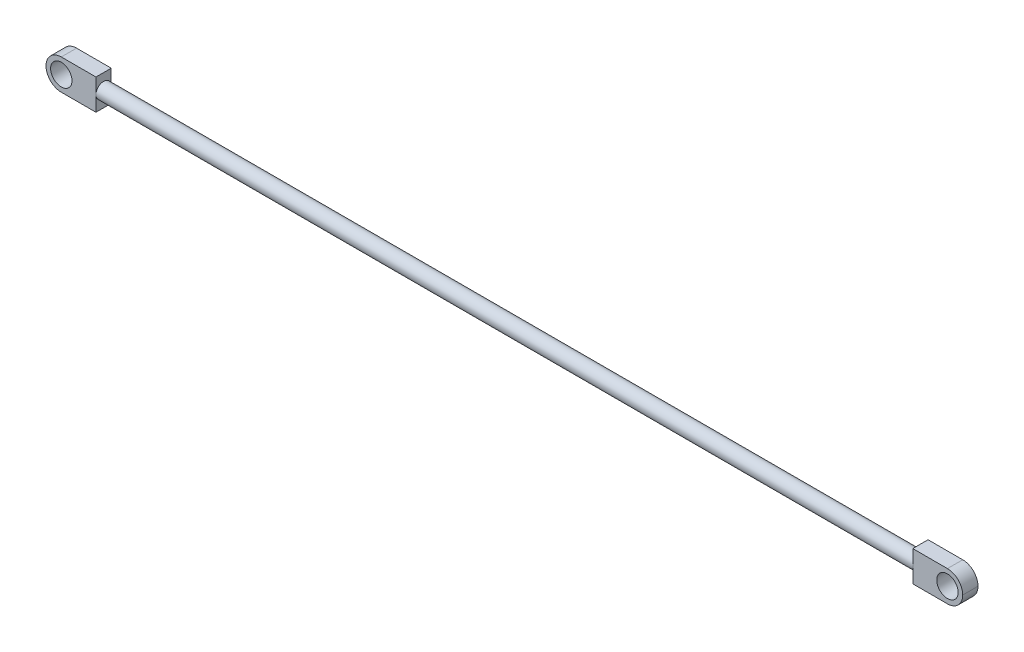
SolidWorks part; units mm, degrees
ref_plane "前视基准面" through (0, 0, 0) normal (0, 0, 1) x (1, 0, 0)
ref_plane "上视基准面" through (0, 0, 0) normal (0, 1, 0) x (1, 0, 0)
ref_plane "右视基准面" through (0, 0, 0) normal (1, 0, 0) x (0, 0, -1)
other "Configuration Table"
sketch "草图1" plane through (0, 0, 0) normal (0, 0, 1) x (1, 0, 0)
  line L1 (-300, -10) -> (300, -10)
  line L2 (-300, -10) -> (-300, 10)
  line L3 (-300, 10) -> (300, 10)
  line L4 (300, -10) -> (300, 10)
  line L5 (-300, -10) -> (300, 10) construction
  line L6 (-300, 10) -> (300, -10) construction
  circle A0 centre (-290, 0) radius 7
  circle A1 centre (290, 0) radius 7
  point P0 (0, 0)
  dimension "D3" = 14
  dimension "D4" = 14
  dimension "D1" = 20
  dimension "D2" = 600
  dimension "D5" = 290
  dimension "D6" = 290
extrude "凸台-拉伸1" add sketch "草图1" along normal blind 10
fillet "圆角1" radius 10 4 edges at (300, 10, 5) (300, -10, 5) (-300, -10, 5) (-300, 10, 5)
sketch "Sketch1" plane through (0, 0, 0) normal (0, 0, 1) x (1, 0, 0)
  line L1 (-267.2981, -20.9331) -> (267.2981, -20.9331)
  line L2 (-267.2981, -20.9331) -> (-267.2981, 20.9331)
  line L3 (-267.2981, 20.9331) -> (267.2981, 20.9331)
  line L4 (267.2981, -20.9331) -> (267.2981, 20.9331)
  line L5 (-267.2981, -20.9331) -> (267.2981, 20.9331) construction
  line L6 (-267.2981, 20.9331) -> (267.2981, -20.9331) construction
  point P0 (0, 0)
extrude "Cut-Extrude1" cut sketch "Sketch1" along normal blind 19
sketch "Sketch2" plane through (-267.2981, 0, 0) normal (1, 0, 0) x (0, 0, -1)
  line L0 (-10, 0) -> (0, 0) construction
  circle A0 centre (-5, 0) radius 5
extrude "Boss-Extrude1" add sketch "Sketch2" along normal blind 535
